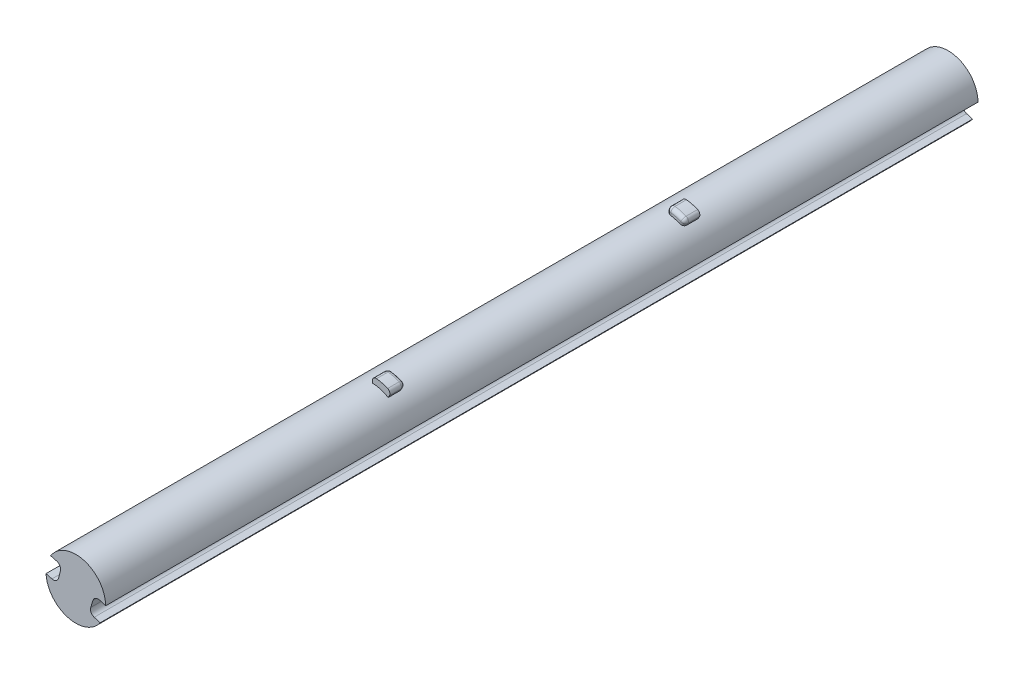
SolidWorks part; units mm, degrees
ref_plane "Płaszczyzna przednia" through (0, 0, 0) normal (0, 0, 1) x (1, 0, 0)
ref_plane "Płaszczyzna górna" through (0, 0, 0) normal (0, 1, 0) x (1, 0, 0)
ref_plane "Płaszczyzna prawa" through (0, 0, 0) normal (1, 0, 0) x (0, 0, -1)
sketch "Szkic1" plane through (0, 0, 0) normal (0, 0, 1) x (1, 0, 0)
  circle A0 centre (0, 0) radius 3.9
  dimension "D1" = 7.8
extrude "Dodanie-wyciągnięcie1" add sketch "Szkic1" along normal blind 114
ref_plane "Płaszczyzna2" through (0, 0, 106) normal (0, 0, 1) x (1, 0, 0)
sketch "Szkic4" plane through (0, 0, 0) normal (1, 0, 0) x (0, 0, -1)
  line L0 (-103, -0.2826) -> (-102, -0.2826) construction
  line L1 (-102, -0.2826) -> (-83, -0.2826) construction
  line L2 (-83, -0.2826) -> (-27, -0.2826) construction
  line L3 (-83, -0.2826) -> (-75.25, -0.2826)
  line L4 (-27, -0.2826) -> (-8, -0.2826) construction
  line L5 (-8, -0.2826) -> (0, -0.2826) construction
  line L6 (0, -3.9) -> (0, 3.9) construction
  line L7 (-75.25, -0.2826) -> (-34.75, -0.2826)
  line L8 (-34.75, -0.2826) -> (-27, -0.2826)
  line L10 (-75.25, -0.2826) -> (-73.25, -0.2826)
  line L11 (-75.25, -0.2826) -> (-75.25, 4.7174)
  line L12 (-75.25, 4.7174) -> (-73.25, 4.7174)
  line L13 (-73.25, -0.2826) -> (-73.25, 4.7174)
  line L14 (-34.75, -0.2826) -> (-36.75, -0.2826)
  line L15 (-34.75, -0.2826) -> (-34.75, 4.7174)
  line L16 (-34.75, 4.7174) -> (-36.75, 4.7174)
  line L17 (-36.75, -0.2826) -> (-36.75, 4.7174)
  dimension "D1" = 1
  dimension "D2" = 8
  dimension "D4" = 7.75
revolve "Obrót1" add sketch "Szkic4" angle 30 about L7
fillet "Zaokrąglenie5" radius 0.5 10 edges at (0, 4.7174, 74.25) (2.5, 4.0475, 74.25) (0, 4.3087, 73.25) (2.2855, 3.6761, 73.25) (1.2941, 4.547, 73.25) (0, 4.3087, 36.75) (2.2855, 3.6761, 36.75) (1.2941, 4.547, 36.75) (2.5, 4.0475, 35.75) (0, 4.7174, 35.75)
sketch "Szkic5" plane through (0, 0, 114) normal (0, 0, 1) x (1, 0, 0)
  line L0 (3.7193, -1.1735) -> (4.0202, -0.2198)
  line L1 (4.0202, -0.2198) -> (3.0665, 0.0811)
  line L2 (2.4392, -0.2453) -> (2.1383, -1.199)
  line L3 (2.4647, -1.8263) -> (3.4184, -2.1272)
  line L4 (3.4184, -2.1272) -> (3.7193, -1.1735)
  line L5 (3.7193, -1.1735) -> (0, 0) construction
  line L6 (2.2485, -0.1851) -> (1.9476, -1.1388)
  line L7 (2.4045, -2.017) -> (3.5489, -2.3781)
  line L8 (3.5489, -2.3781) -> (3.91, -1.2337)
  line L9 (3.91, -1.2337) -> (4.2711, -0.0893)
  line L10 (4.2711, -0.0893) -> (3.1267, 0.2718)
  line L11 (1.0775, 3.7482) -> (-1.0775, -3.7482)
  line L12 (-3.6665, 2.1925) -> (-2.505, 1.8907)
  line L13 (-3.9682, 1.0311) -> (-3.6665, 2.1925)
  line L14 (-4.27, -0.1304) -> (-3.9682, 1.0311)
  line L15 (-3.1086, -0.4322) -> (-4.27, -0.1304)
  line L16 (-2.0036, 1.0372) -> (-2.255, 0.0693)
  line L17 (-4.0261, 0.0129) -> (-3.7747, 0.9808)
  line L18 (-3.0583, -0.2386) -> (-4.0261, 0.0129)
  line L19 (-2.1971, 1.0875) -> (-2.4486, 0.1196)
  line L20 (-3.5232, 1.9486) -> (-2.5553, 1.6971)
  line L21 (-3.7747, 0.9808) -> (-3.5232, 1.9486)
  circle A0 centre (0, 0) radius 3.9 construction
  arc A1 (3.0665, 0.0811) -> (2.4392, -0.2453) centre (2.9161, -0.3958) ccw
  arc A2 (2.1383, -1.199) -> (2.4647, -1.8263) centre (2.6152, -1.3494) ccw
  arc A3 (1.9476, -1.1388) -> (2.4045, -2.017) centre (2.6152, -1.3494) ccw
  arc A4 (3.1267, 0.2718) -> (2.2485, -0.1851) centre (2.9161, -0.3958) ccw
  arc A5 (2.0711, 3.3046) -> (0, 3.9) centre (0, 0) ccw construction
  arc A6 (-2.505, 1.8907) -> (-2.0036, 1.0372) centre (-2.6811, 1.2132) cw
  arc A7 (-2.255, 0.0693) -> (-3.1086, -0.4322) centre (-2.9325, 0.2454) cw
  arc A8 (-2.4486, 0.1196) -> (-3.0583, -0.2386) centre (-2.9325, 0.2454) cw
  arc A9 (-2.5553, 1.6971) -> (-2.1971, 1.0875) centre (-2.6811, 1.2132) cw
  dimension "D3" = 0.5
  dimension "D1" = 2
  dimension "D2" = 1.5
  dimension "D4" = 0.2
extrude "Wytnij-wyciągnięcie1" cut sketch "Szkic5" against normal blind 114 contours A4 L6 A3 L7 L8 L9 L10
extrude "Wytnij-wyciągnięcie2" cut sketch "Szkic5<3>" against normal blind 11.5 contours L12 A6 L16 A7 L15 L14 L13
sketch "Szkic5<3>" plane through (0, 0, 114) normal (0, 0, 1) x (1, 0, 0) same geometry as "Szkic5"
